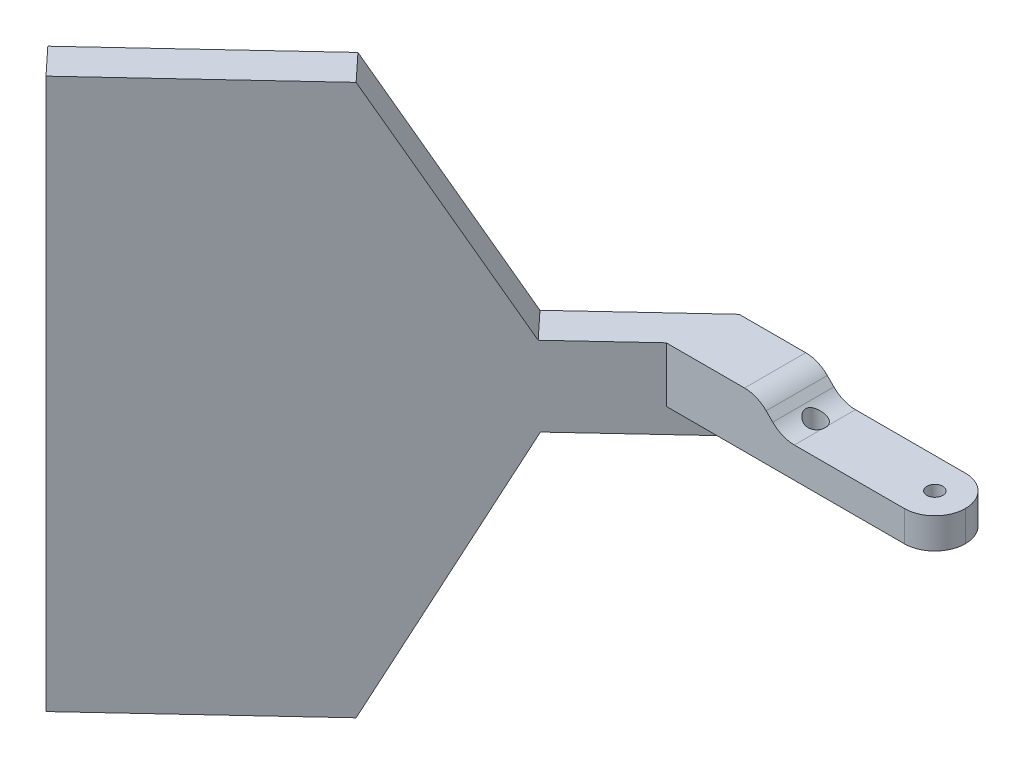
SolidWorks part; units mm, degrees
ref_plane "Front" through (0, 0, 0) normal (0, 0, 1) x (1, 0, 0)
ref_plane "Top" through (0, 0, 0) normal (0, 1, 0) x (1, 0, 0)
ref_plane "Right" through (0, 0, 0) normal (1, 0, 0) x (0, 0, -1)
sketch "Sketch1" plane through (0, 0, 0) normal (0, 1, 0) x (1, 0, 0)
  line L0 (0, 10) -> (0, 0)
  line L1 (0, 0) -> (42, 0)
  line L3 (0, 10) -> (42, 10)
  line L4 (42, 0) -> (42, 10)
  line L9 (0, 10) -> (-58.5083, -44.5599)
  line L10 (-58.5083, -44.5599) -> (-54.4163, -48.948)
  line L11 (0, 10) -> (4.092, 5.6119)
  line L12 (-54.4163, -48.948) -> (4.092, 5.6119)
  line L13 (0, 0) -> (-1.926, 0)
  line L14 (-1.926, 0) -> (0, 1.796)
  line L15 (0, 1.796) -> (0, 0)
  dimension "D1" = 10
  dimension "D2" = 42
  dimension "D3" = 223
  dimension "D4" = 80
  dimension "D5" = 6
  dimension "D6" = 270
extrude "Boss-Extrude1" add sketch "Sketch1" along normal blind 5 contours L10 L12 L1 L0 L9 | L1 L12 L11 L0 | L12 L1 L4 L3 L11 | L13 L0 L12 region at (1.364, 0, -5.8026) region at (-28.2435, 0, 20.3899) region at (21.8174, 0, -4.9666) region at (-0.642, 0, -0.5987)
fillet "Fillet1" radius 5 2 edges at (42, 2.5, 0) (42, 2.5, -10)
sketch "Sketch2" plane through (0, 5, 0) normal (0, 1, 0) x (1, 0, 0)
  circle A0 centre (37, 5) radius 1.3
extrude "Cut-Extrude1" cut sketch "Sketch2" against normal blind 10
sketch "Sketch3" plane through (0, 5, 0) normal (0, 1, 0) x (1, 0, 0)
  line L0 (-58.5083, -44.5599) -> (-54.4163, -48.948)
  line L1 (-54.4163, -48.948) -> (-28.1712, -24.474)
  line L2 (-54.4163, -48.948) -> (-1.926, 0) construction
  line L3 (-28.1712, -24.474) -> (-32.2631, -20.0859)
  line L4 (0, 10) -> (-58.5083, -44.5599) construction
  line L5 (-32.2631, -20.0859) -> (-58.5083, -44.5599)
extrude "Boss-Extrude2" add sketch "Sketch3" along normal blind 40
sketch "Sketch4" plane through (0, 0, 0) normal (0, -1, 0) x (1, 0, 0)
  line L0 (-58.5083, 44.5599) -> (-54.4163, 48.948)
  line L1 (-54.4163, 48.948) -> (-28.1712, 24.474)
  line L2 (-54.4163, 48.948) -> (-1.926, 0) construction
  line L3 (-28.1712, 24.474) -> (-32.2631, 20.0859)
  line L4 (0, -10) -> (-58.5083, 44.5599) construction
  line L5 (-32.2631, 20.0859) -> (-58.5083, 44.5599)
extrude "Boss-Extrude3" add sketch "Sketch4" along normal blind 45
sketch "Sketch5" plane through (-4.9878, 0, -5.3488) normal (-0.682, 0, -0.7314) x (-0.7314, 0, 0.682)
  line L0 (37.2943, -45) -> (37.2943, 0)
  line L1 (37.2943, 0) -> (13.889, 0)
  line L2 (-6.82, 0) -> (37.2943, 0) construction
  line L3 (13.889, 0) -> (37.2943, -45)
  line L4 (13.889, 5) -> (37.2943, 45)
  line L5 (-6.82, 5) -> (37.2943, 5) construction
  line L6 (37.2943, 45) -> (37.2943, 5)
  line L7 (37.2943, 5) -> (13.889, 5)
extrude "Boss-Extrude4" add sketch "Sketch5" against normal blind 6
sketch "Sketch6" plane through (0, 0, 0) normal (0, -1, 0) x (1, 0, 0)
  circle A0 centre (37, -5) radius 4.9
  circle A1 centre (37, -5) radius 1.3
extrude "Boss-Extrude5" [suppressed] add sketch "Sketch6" along normal blind 0.9
sketch "Sketch8" plane through (0, 0, 0) normal (0, -1, 0) x (1, 0, 0)
  line L0 (0, -10) -> (-23.7044, 12.1047)
  line L1 (-32.2631, 20.0859) -> (-15.1456, 4.1235) construction
  line L6 (-23.7044, 12.1047) -> (-19.6124, 16.4928)
  line L7 (-28.1712, 24.474) -> (-11.0536, 8.5116) construction
  line L8 (-19.6124, 16.4928) -> (8.7977, -10)
  line L9 (0, -10) -> (37, -10) construction
  line L10 (8.7977, -10) -> (0, -10)
extrude "Boss-Extrude6" add sketch "Sketch8" along normal blind 4
sketch "Sketch9" plane through (0, 5, 0) normal (0, 1, 0) x (1, 0, 0)
  line L3 (-16.6671, -5.5424) -> (-32.2631, -20.0859) construction
  line L4 (-24.4651, -12.8141) -> (0, 10)
  line L6 (-24.4651, -12.8141) -> (-16.7996, -13.8699)
  line L7 (-28.1712, -24.474) -> (-11.0536, -8.5116) construction
  line L9 (-16.7996, -13.8699) -> (8.7977, 10)
  line L10 (0, 10) -> (37, 10) construction
  line L11 (8.7977, 10) -> (0, 10)
  line L12 (37, 0) -> (-1.926, 0) construction
  line L13 (8.7977, 0) -> (-1.926, 0)
  line L14 (-1.926, 0) -> (8.7977, 10)
  line L15 (8.7977, 10) -> (17.9505, 10)
  line L16 (17.9505, 10) -> (17.9505, 0)
  line L17 (17.9505, 0) -> (8.7977, 0)
  line M1 (-15.1456, -4.1235) -> (-11.0536, -8.5116)
  line M2 (-11.0536, -8.5116) -> (-1.926, 0)
  line M3 (-1.926, 0) -> (37, 0)
  line M6 (37, 10) -> (0, 10)
  line M7 (0, 10) -> (-15.1456, -4.1235)
extrude "Boss-Extrude7" add sketch "Sketch9" along normal blind 4 contours L9 M3 | L9 M2 M6 M7 M1 | L6 L9 L4 M1 region at (-17.0984, 5, 9.7222) region at (-4.2059, 5, -1.7921) region at (10.3631, 5, -4.3843)
fillet "Fillet2" [suppressed] radius 15
fillet "Fillet7" radius 5 1 edges at (17.9505, 9, -5) profile chamfer
fillet "Fillet8" radius 5 2 edges at (12.9505, 9, -5) (16.9505, 5, -5)
sketch "Sketch11" plane through (0, 0, 0) normal (0, -1, 0) x (-1, 0, 0)
  circle A0 centre (-17.5, 5) radius 1.6
extrude "Cut-Extrude2" cut sketch "Sketch11" against normal blind 10
